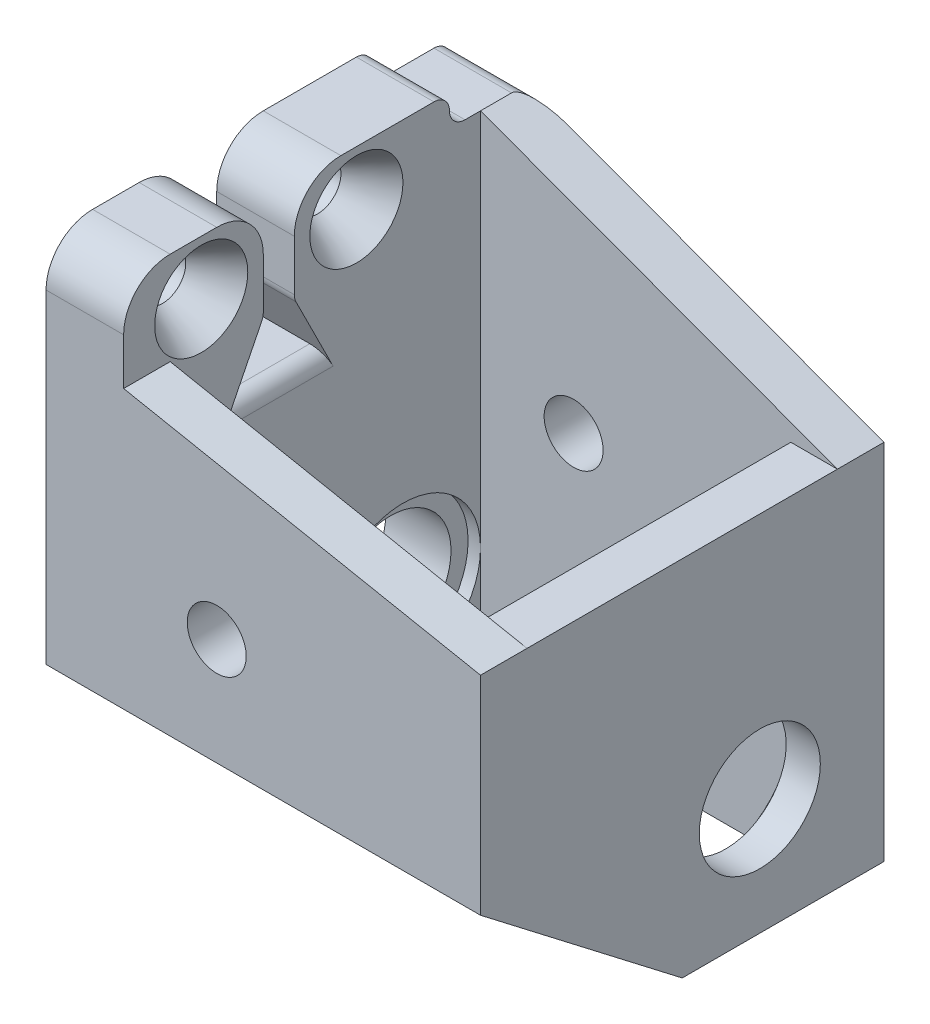
SolidWorks part; units mm, degrees
other "标注1"
sketch "草图49" plane through (13, 10.3992, -3) normal (0.763, 0.5413, -0.3534) x (-0.4894, 0.1265, -0.8629)
material "ABS"
ref_plane "前视基准面" through (0, 0, 0) normal (0, 0, 1) x (1, 0, 0)
ref_plane "上视基准面" through (0, 0, 0) normal (0, 1, 0) x (1, 0, 0)
ref_plane "右视基准面" through (0, 0, 0) normal (1, 0, 0) x (0, 0, -1)
sketch "草图1" plane through (0, 0, 0) normal (0, 0, 1) x (1, 0, 0)
  line L0 (10, 0) -> (-10, 0)
  line L1 (0, 4.2473) -> (0, -34.6143) construction
  line L2 (-10, 0) -> (-10, -57.766)
  line L3 (-10, -57.766) -> (10, -57.766)
  line L4 (10, 0) -> (10, -57.766)
  point P8 (0, -57.766)
  point P9 (0, 0)
extrude "凸台-拉伸1" add sketch "草图1" against normal blind 3
sketch "草图2" plane through (-10, 0, 0) normal (-1, 0, 0) x (0, 0, 1)
  line L1 (-3, 0) -> (23, 0)
  line L2 (-3, 0) -> (-3, -57.766)
  line L3 (-3, -57.766) -> (23, -57.766)
  line L4 (23, 0) -> (23, -57.766)
extrude "凸台-拉伸2" add sketch "草图2" along normal blind 3
sketch "草图3" plane through (0, 0, 0) normal (0, 0, 1) x (1, 0, 0)
  line L0 (-10, -5.5) -> (10, -5.5)
  line L1 (-10, -57.766) -> (-10, 0) construction
  line L2 (10, -57.766) -> (10, 0) construction
  line L3 (10, 0) -> (-10, 0) construction
  dimension "D1" = 5.5
sketch "草图4" plane through (-10, 0, 0) normal (1, 0, 0) x (0, 0, -1)
  line L0 (-23, -5.5) -> (0, -5.5)
  line L1 (-23, -57.766) -> (-23, 0) construction
  line L2 (0, 0) -> (0, -57.766) construction
  line L3 (-23, 0) -> (0, 0) construction
  dimension "D1" = 5.5
sketch "草图7" plane through (-10, 0, 0) normal (1, 0, 0) x (0, 0, -1)
  line L0 (-23, -14.9) -> (0, -14.9)
  line L1 (-23, -57.766) -> (-23, 0) construction
  line L2 (0, -57.766) -> (0, 0) construction
  line L3 (-23, -5.5) -> (0, -5.5) construction
  circle A0 centre (-5, -14.9) radius 3.9
  point P8 (-5, -14.9)
  dimension "D1" = 9.4
  dimension "D2" = 5
extrude "切除-拉伸1" cut sketch "草图7" against normal blind 6 contours L0 A0 | L0 A0 region at (-10, -13.2448, 5) region at (-10, -16.5552, 5)
sketch "草图8" plane through (-13, 0, 0) normal (-1, 0, 0) x (0, 0, 1)
  circle A0 centre (5, -14.9) radius 4.48
extrude "切除-拉伸2" cut sketch "草图8" against normal blind 0.8
sketch "草图9" plane through (0, 0, 0) normal (0, 0, 1) x (1, 0, 0)
  line L0 (-10, -5.5) -> (10, -5.5) construction
  circle A0 centre (-4, -5.5) radius 1.9
  point P0 (-4, -5.5)
  point P1 (-10, -5.5)
  point P4 (-4, -5.5)
  dimension "D1" = 6
extrude "切除-拉伸3" cut sketch "草图9" against normal blind 3.8
sketch "草图10" plane through (0, 0, 0) normal (0, 0, 1) x (1, 0, 0)
  line L0 (0, 1.0359) -> (0, 0) construction
  line L1 (0, 0) -> (0, -59.324) construction
ref_plane "基准面1" through (0, 0, 0) normal (1, 0, 0) x (0, 0, -1)
mirror "镜向1" about plane through (0, 0, 0) normal (1, 0, 0) of "凸台-拉伸2"
mirror "镜向2" about plane through (0, 0, 0) normal (1, 0, 0) of "切除-拉伸1", "切除-拉伸2"
ref_plane "基准面2" through (0, 0, 10) normal (0, 0, 1) x (1, 0, 0)
mirror "镜向3" about plane through (0, 0, 10) normal (0, 0, 1) of "凸台-拉伸1"
mirror "镜向5" about plane through (0, 0, 10) normal (0, 0, 1) of "切除-拉伸3"
sketch "草图12" plane through (13, 0, 0) normal (1, 0, 0) x (0, 0, -1)
  line L0 (-23, -22.4) -> (3, -22.4)
  line L1 (-23, -57.766) -> (-23, 0) construction
  line L2 (3, 0) -> (3, -57.766) construction
  line L5 (-23, -22.4) -> (-23, -57.766)
  line L6 (-23, -57.766) -> (3, -57.766)
  line L7 (3, -22.4) -> (3, -57.766)
  circle A0 centre (-5, -14.9) radius 3.9 construction
  dimension "D1" = 7.5
extrude "切除-拉伸4" cut sketch "草图12" against normal blind 36
sketch "草图22" plane through (13, 0, 0) normal (1, 0, 0) x (0, 0, -1)
  line L0 (-23, -12.4) -> (-23, -22.4)
  line L1 (-23, -22.4) -> (-23, 0) construction
  line L2 (-23, -22.4) -> (-10, -22.4)
  line L3 (3, -22.4) -> (-23, -22.4) construction
  line L4 (-23, -12.4) -> (-10, -22.4)
extrude "切除-拉伸8" cut sketch "草图22" against normal blind 28
sketch "草图23" plane through (0, 0, 0) normal (0, 1, 0) x (1, 0, 0)
  line L1 (-10, 0) -> (10, 0)
  line L2 (-10, 0) -> (-10, -20)
  line L3 (-10, -20) -> (10, -20)
  line L4 (10, 0) -> (10, -20)
  line L5 (13, -23) -> (-13, -23)
  line L6 (13, -23) -> (13, 3)
  line L7 (13, 3) -> (-13, 3)
  line L8 (-13, -23) -> (-13, 3)
extrude "凸台-拉伸7" add sketch "草图23" along normal blind 4
sketch "草图24" plane through (0, 4, 0) normal (0, 1, 0) x (1, 0, 0)
  line L0 (10, -20) -> (10, 0) construction
  line L1 (-10, 0) -> (10, 0)
  line L2 (-10, 0) -> (-10, -20)
  line L3 (-10, -20) -> (10, -20)
  line L4 (10, 0) -> (10, -20)
extrude "凸台-拉伸8" add sketch "草图24" against normal blind 3
sketch "草图25" plane through (0, 4, 0) normal (0, 1, 0) x (1, 0, 0)
  line L0 (13, -23) -> (13, 3) construction
  line L4 (13, -23) -> (18, -23)
  line L5 (13, -23) -> (13, -7)
  line L6 (13, -7) -> (18, -7)
  line L7 (18, -23) -> (18, -7)
  circle A0 centre (15.5, -20.2333) radius 1.5
  circle A1 centre (15.5, -10.2333) radius 1.5
  point P0 (13, -15)
  dimension "D1" = 8
extrude "凸台-拉伸9" add sketch "草图25" against normal blind 3 contours A1 | A0 | L5 L4 L7 L6 region at (15.5, 4, 20.2333) region at (15.5, 4, 10.2333)
fillet "圆角1" radius 1 1 edges at (18, 1, 15)
sketch "草图26" plane through (13, 0, 0) normal (1, 0, 0) x (0, 0, -1)
  line L0 (-23, 1) -> (-7, 1) construction
  line L1 (-16, 1) -> (-14, 1)
  arc A0 (-16, 1) -> (-14, 1) centre (-15, 1) ccw
extrude "切除-拉伸9" cut sketch "草图26" against normal blind 3
sketch "草图27" plane through (0, 4, 0) normal (0, 1, 0) x (1, 0, 0)
  circle A0 centre (7.5, -15.2333) radius 1.5
extrude "切除-拉伸10" cut sketch "草图27" against normal blind 3
sketch "草图28" plane through (0, 1, 0) normal (0, -1, 0) x (1, 0, 0)
  line L1 (-10, 20) -> (10, 20)
  line L2 (-10, 20) -> (-10, 0)
  line L3 (-10, 0) -> (10, 0)
  line L4 (10, 20) -> (10, 0)
extrude "切除-拉伸11" cut sketch "草图28" against normal blind 10
sketch "草图29" plane through (0, 0, -3) normal (0, 0, -1) x (-1, 0, 0)
  line L1 (13, 4) -> (-24.6816, 4)
  line L2 (13, 4) -> (13, 1)
  line L3 (13, 1) -> (-24.6816, 1)
  line L4 (-24.6816, 4) -> (-24.6816, 1)
extrude "切除-拉伸12" cut sketch "草图29" against normal blind 42
sketch "草图31" plane through (-12.2, 0, 0) normal (-1, 0, 0) x (0, 0, 1)
  circle A0 centre (5, -14.9) radius 3.98
  circle A1 centre (5, -14.9) radius 4.48
extrude "凸台-拉伸13" add sketch "草图31" along normal blind 0.8
sketch "草图32" plane through (-10, 0, 0) normal (1, 0, 0) x (0, 0, -1)
  circle A0 centre (-5, -14.9) radius 3.98
  circle A1 centre (-5, -14.9) radius 5
extrude "切除-拉伸13" cut sketch "草图32" against normal blind 0.8
sketch "草图33" plane through (13, 0, 0) normal (1, 0, 0) x (0, 0, -1)
  circle A0 centre (-5, -14.9) radius 4.48
extrude "凸台-拉伸14" add sketch "草图33" against normal blind 3
mirror "镜向6" about plane through (0, 0, 0) normal (1, 0, 0) of "切除-拉伸1", "切除-拉伸13"
sketch "草图36" plane through (-10.8, 0, 0) normal (1, 0, 0) x (0, 0, -1)
  circle A0 centre (-5, -14.9) radius 5
extrude "切除-拉伸14" cut sketch "草图36" along normal blind 3
mirror "镜向7" about plane through (0, 0, 0) normal (1, 0, 0) of "切除-拉伸14"
sketch "草图37" plane through (-12.2, 0, 0) normal (-1, 0, 0) x (0, 0, 1)
  circle A0 centre (5, -14.9) radius 3.9
  circle A1 centre (5, -14.9) radius 3.98
extrude "凸台-拉伸17" add sketch "草图37" along normal up to surface (0.8 mm away) up to face at (-13, -11.04, 10)
sketch "草图38" plane through (-13, 0, 0) normal (-1, 0, 0) x (0, 0, 1)
  line L0 (13, 1) -> (13, 8)
  line L1 (23, 1) -> (-3, 1) construction
  line L3 (11, 10.3992) -> (5, 10.3992)
  line L4 (15, 1) -> (21, 1)
  line L5 (15, 1) -> (15, 10.3992)
  line L6 (15, 10.3992) -> (21, 10.3992)
  line L7 (21, 1) -> (21, 10.3992)
  line L8 (5, 1) -> (5, 10.3992)
  line L9 (11, 1) -> (5, 1)
  line L10 (11, 1) -> (11, 10.3992)
  circle A0 centre (18, 8) radius 1.5
  circle A2 centre (8, 8) radius 1.5
  line M9 (23, 1) -> (-3, 1)
  dimension "D1" = 2
  dimension "D2" = 3
  dimension "D3" = 6
extrude "凸台-拉伸18" add sketch "草图38" against normal blind 3 contours L7 L6 L5 A0 M9 | L10 L3 L8 A2 M9 region at (-13, 5.37, 8) region at (-13, 5.37, 18)
sketch "草图39" plane through (13, 0, 0) normal (1, 0, 0) x (0, 0, -1)
  line L0 (-23, 1) -> (-16, 1) construction
  line L1 (-17.3818, 1) -> (-13.1942, 1)
  line L2 (-17.3818, 1) -> (-17.3818, -0.3609)
  line L3 (-17.3818, -0.3609) -> (-13.1942, -0.3609)
  line L4 (-13.1942, 1) -> (-13.1942, -0.3609)
extrude "凸台-拉伸19" add sketch "草图39" against normal blind 3
sketch "草图43" plane through (-13, 0, 0) normal (-1, 0, 0) x (0, 0, 1)
  line L0 (-3, 1) -> (5, 1)
  line L1 (5, 1) -> (5, 10.3992)
  line L2 (5, 10.3992) -> (11, 10.3992)
  line L3 (11, 10.3992) -> (11, 1)
  line L4 (11, 1) -> (15, 1)
  line L5 (15, 1) -> (15, 10.3992)
  line L6 (15, 10.3992) -> (21, 10.3992)
  line L7 (21, 10.3992) -> (21, 1)
  line L8 (21, 1) -> (23, 1)
  line L9 (23, 1) -> (23, -12.4)
  line L10 (23, -12.4) -> (10, -22.4)
  line L11 (10, -22.4) -> (-3, -22.4)
  line L12 (-3, -22.4) -> (-3, 1)
  circle A0 centre (8, 8) radius 1.5
  circle A1 centre (18, 8) radius 1.5
  circle A2 centre (5, -14.9) radius 3.9
extrude "凸台-拉伸22" add sketch "草图43" along normal blind 2
sketch "草图44" plane through (0, 0, 21) normal (0, 0, 1) x (1, 0, 0)
  line L1 (-15, 10.3992) -> (-10, 10.3992)
  line L2 (-15, 10.3992) -> (-15, 1)
  line L3 (-15, 1) -> (-10, 1)
  line L4 (-10, 10.3992) -> (-10, 1)
extrude "凸台-拉伸23" add sketch "草图44" along normal up to surface (2 mm away) up to face at (-4, -3.6, 23)
sketch "草图45" plane through (0, 0, 23) normal (0, 0, 1) x (1, 0, 0)
  line L1 (-10, 1) -> (13, 1)
  line L3 (-10, 1) -> (-10, 5.5)
  line L7 (-10, 10.3992) -> (-10, 1) construction
  line L8 (-10, 5.5) -> (13, 1)
extrude "凸台-拉伸24" add sketch "草图45" against normal up to surface (3 mm away) up to face at (0, -6.8538, 20)
sketch "草图47" plane through (0, 0, 5) normal (0, 0, -1) x (-1, 0, 0)
  line L6 (10, 1) -> (15, 1)
  line L7 (10, 1) -> (10, 10.3992)
  line L8 (10, 10.3992) -> (15, 10.3992)
  line L9 (15, 1) -> (15, 10.3992)
extrude "凸台-拉伸25" add sketch "草图47" along normal up to surface (8 mm away) up to face at (-2.1, -5.5, -3)
sketch "草图51" plane through (0, 10.3992, 0) normal (0, 1, 0) x (1, 0, 0)
  line L1 (-15, 3) -> (-10, 3)
  line L2 (-15, 3) -> (-15, -11)
  line L3 (-15, -11) -> (-10, -11)
  line L4 (-10, 3) -> (-10, -11)
  line L5 (-15, -15) -> (-10, -15)
  line L6 (-15, -15) -> (-15, -23)
  line L7 (-15, -23) -> (-10, -23)
  line L8 (-10, -15) -> (-10, -23)
extrude "凸台-拉伸28" add sketch "草图51" along normal blind 1.1
sketch "草图53" plane through (-10, 0, 0) normal (1, 0, 0) x (0, 0, -1)
  line L1 (3, 11.4992) -> (-2, 11.4992)
  line L2 (3, 11.4992) -> (3, 9.4992)
  line L3 (3, 9.4992) -> (-2, 9.4992)
  line L4 (-2, 11.4992) -> (-2, 9.4992)
extrude "切除-拉伸16" cut sketch "草图53" against normal blind 6.1
fillet "圆角9" radius 1 2 edges at (-12.5, 9.4992, 2) (-12.5, 11.4992, 2)
sketch "草图54" plane through (0, 0, -3) normal (0, 0, -1) x (-1, 0, 0)
  line L0 (-13, 1) -> (10, 1)
  line L1 (10, 1) -> (10, 9.4992)
  line L2 (10, 9.4992) -> (-13, 1)
extrude "凸台-拉伸30" add sketch "草图54" against normal up to surface (3 mm away) up to face at (0, -12.1, 0)
fillet "圆角10" radius 1 1 edges at (-12.5, 9.4992, -3)
sketch "草图56" plane through (-10, 0, 0) normal (1, 0, 0) x (0, 0, -1)
  circle A0 centre (-18, 8) radius 3
  circle A1 centre (-8, 8) radius 3
sketch "草图57" plane through (0, 0, 15) normal (0, 0, -1) x (-1, 0, 0)
  line L6 (15, 1) -> (10, 1)
  line L7 (15, 1) -> (15, 11.4992)
  line L8 (15, 11.4992) -> (10, 11.4992)
  line L9 (10, 1) -> (10, 11.4992)
extrude "凸台-拉伸31" add sketch "草图57" along normal blind 1
sketch "草图58" plane through (0, 0, 11) normal (0, 0, 1) x (1, 0, 0)
  line L1 (-15, 11.4992) -> (-10, 11.4992)
  line L2 (-15, 11.4992) -> (-15, 1)
  line L3 (-15, 1) -> (-10, 1)
  line L4 (-10, 11.4992) -> (-10, 1)
extrude "凸台-拉伸32" add sketch "草图58" along normal blind 1
sketch "草图59" plane through (-10, 0, 0) normal (1, 0, 0) x (0, 0, -1)
  circle A0 centre (-18, 8) radius 3.1
  circle A1 centre (-8, 8) radius 3.1
fillet "圆角11" radius 3 3 edges at (-12.5, 11.4992, 12) (-12.5, 11.4992, 14) (-12.5, 11.4992, 23)
sketch "草图61" plane through (-10, 0, 0) normal (1, 0, 0) x (0, 0, -1)
  line L0 (-12, 1) -> (-12, 5)
  line L1 (-12, 1) -> (-12, 8.4992) construction
  line L2 (-12, 5) -> (-10, 1)
  line L3 (-10, 1) -> (-12, 1)
  line L4 (-14, 1) -> (-14, 5)
  line L5 (-14, 8.4992) -> (-14, 1) construction
  line L6 (-14, 5) -> (-16, 1)
  line L7 (-16, 1) -> (-14, 1)
extrude "切除-拉伸19" cut sketch "草图61" against normal blind 6.5
fillet "圆角14" radius 1 1 edges at (-10, 1, 13)
fillet "圆角19" radius 1 2 edges at (-12.5, 5, 12) (-12.5, 5, 14)
hole_wizard "打孔尺寸(%根据)内六角花形沉头螺钉的类型1" positions "3D草图1" profile "草图62" countersink size "M6" standard "GB" end condition up to next
sketch3d "3D草图1"
  line L0 (-10, 8, 18) -> (-15, 8, 18) construction
  line L1 (-10, 8, 8) -> (-15, 8, 8) construction
  point P0 (-10, 8, 18)
  point P4 (-10, 8, 8)
sketch "草图62" plane through (-10, 8, 18) normal (0, 1, 0) x (0, 0, -1)
  line L0 (0, 0) -> (0, 5)
  line L1 (0, 5) -> (1.5, 5)
  line L2 (1.5, 5) -> (1.5, 2.4964)
  line L3 (1.5, 2.4964) -> (3, 0)
  line L5 (3, 0) -> (0, 0)
  line L6 (-1.5, 2.4964) -> (-3, 0) construction
  line L11 (0, -6.35) -> (0, 107.95) construction
  dimension "通孔孔直径" = 3
  dimension "通孔孔深度" = 5
  dimension "近端锥形沉头孔直径" = 6
  dimension "近端锥形沉头孔角度" = 62
